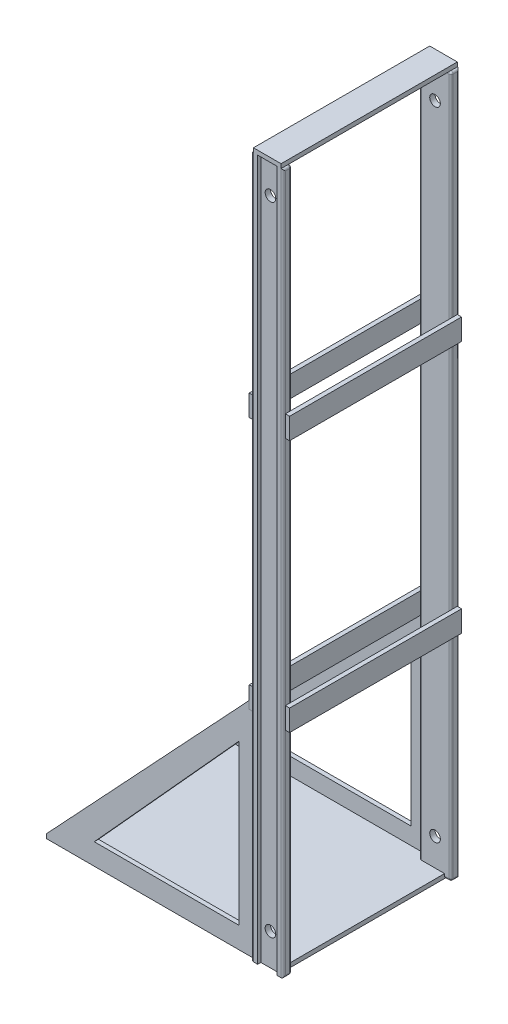
SolidWorks part; units mm, degrees
ref_plane "Front Plane" through (0, 0, 0) normal (0, 0, 1) x (1, 0, 0)
ref_plane "Top Plane" through (0, 0, 0) normal (0, 1, 0) x (1, 0, 0)
ref_plane "Right Plane" through (0, 0, 0) normal (1, 0, 0) x (0, 0, -1)
sketch "Sketch1" plane through (0, 0, 0) normal (0, 0, 1) x (1, 0, 0)
  line L1 (0, 0) -> (15, 0)
  line L2 (0, 0) -> (0, 330)
  line L3 (0, 330) -> (15, 330)
  line L4 (15, 0) -> (15, 330)
  dimension "D1" = 330
  dimension "D2" = 15
extrude "slider_body" add sketch "Sketch1" along normal blind 4 contours L4 L3 L2 L1
sketch "Sketch2" plane through (0, 0, 0) normal (0, 0, -1) x (-1, 0, 0)
  line L0 (0, 330) -> (-15, 330) construction
  line L1 (-12, 330) -> (-3, 330)
  line L2 (-12, 330) -> (-12, 0)
  line L3 (-12, 0) -> (-3, 0)
  line L4 (-3, 330) -> (-3, 0)
  line L5 (0, 0) -> (-15, 0) construction
  line L6 (-15, 0) -> (-15, 330) construction
  line L7 (0, 0) -> (0, 330) construction
  dimension "D1" = 3
  dimension "D2" = 3
extrude "slider_indents" cut sketch "Sketch2" against normal blind 1.5
fillet "Fillet5" radius 1 4 edges at (0, 165, 4) (7.5, 330, 4) (15, 165, 4) (7.5, 0, 4)
fillet "Fillet6" radius 1 5 edges at (0.2929, 329.7071, 3.7071) (0.2929, 0.2929, 3.7071) (0, 165, 0) (0, 330, 1.5) (0, 0, 1.5)
fillet "Fillet7" radius 1 5 edges at (14.7071, 0.2929, 3.7071) (14.7071, 329.7071, 3.7071) (15, 165, 0) (15, 0, 1.5) (15, 330, 1.5)
sketch "Sketch3" plane through (0, 0, 1.5) normal (0, 0, -1) x (-1, 0, 0)
  line L0 (-15, 1) -> (-15, 329) construction
  line L1 (-3, 330) -> (-12, 330) construction
  line L4 (-12, 0) -> (-3, 0) construction
  circle A0 centre (-7.5, 315) radius 2.5
  circle A1 centre (-7.5, 15) radius 2.5
  point P6 (-7.5, 330)
  point P11 (-4.5862, 4.9686)
  dimension "D2" = 5
  dimension "D5" = 5
  dimension "D1" = 7.5
  dimension "D3" = 15
  dimension "D4" = 7.5
  dimension "D6" = 15
extrude "Cut-Extrude2" cut sketch "Sketch3" against normal blind 4
sketch "Sketch5" plane through (0, 330, 0) normal (0, 1, 0) x (1, 0, 0)
  line L1 (1, 0) -> (14, 0)
  line L2 (1, 0) -> (1, -41.5)
  line L3 (1, -41.5) -> (14, -41.5)
  line L4 (14, 0) -> (14, -41.5)
  dimension "D1" = 41.5
extrude "Boss-Extrude2" add sketch "Sketch5" along normal blind 2
sketch "Sketch7" plane through (0, 0, 0) normal (-1, 0, 0) x (0, 0, 1)
  line L0 (1, 329) -> (1, 1) construction
  line L1 (1, 220) -> (41.5, 220)
  line L2 (1, 220) -> (1, 230)
  line L3 (1, 230) -> (41.5, 230)
  line L4 (41.5, 220) -> (41.5, 230)
  line L5 (3, 330) -> (41.5, 330) construction
  line L6 (0, 0) -> (0, 330) construction
  line L7 (1, 1) -> (3, 1) construction
  line L8 (1, 101) -> (42.5, 101)
  line L9 (1, 101) -> (1, 111)
  line L10 (1, 111) -> (42.5, 111)
  line L11 (42.5, 101) -> (42.5, 111)
  dimension "D1" = 110
  dimension "D2" = 10
  dimension "D3" = 41.5
  dimension "D4" = 110
  dimension "D5" = 41.5
  dimension "D6" = 10
extrude "Boss-Extrude3" add sketch "Sketch7" along normal blind 2
sketch "Sketch9" plane through (15, 0, 0) normal (1, 0, 0) x (0, 0, -1)
  line L0 (-1, 1) -> (-1, 329) construction
  line L1 (-1, 230) -> (-41.5, 230)
  line L2 (-1, 230) -> (-1, 220)
  line L3 (-1, 220) -> (-41.5, 220)
  line L4 (-41.5, 230) -> (-41.5, 220)
  line L7 (-3, 1) -> (-1, 1) construction
  line L8 (-1, 101) -> (-42.5, 101)
  line L9 (-1, 101) -> (-1, 111)
  line L10 (-1, 111) -> (-42.5, 111)
  line L11 (-42.5, 101) -> (-42.5, 111)
  dimension "D1" = 10
  dimension "D2" = 110
  dimension "D3" = 10
  dimension "D4" = 41.5
extrude "Boss-Extrude4" add sketch "Sketch9" along normal blind 2
mirror "Mirror4" about plane through (1, 332, 41.5) normal (0, 0, -1) of "slider_body", "slider_indents", "Fillet5", "Fillet6", "Fillet7", "Cut-Extrude2", "Boss-Extrude2", "Boss-Extrude3", "Boss-Extrude4"
sketch "Sketch11" plane through (0, 0, 81.5) normal (0, 0, 1) x (1, 0, 0)
  line L1 (12, 0) -> (-98, 0)
  line L2 (12, 0) -> (12, 2)
  line L3 (12, 2) -> (-98, 2)
  line L4 (-98, 0) -> (-98, 2)
  dimension "D2" = 110
extrude "Boss-Extrude5" add sketch "Sketch11" against normal blind 83
sketch "Sketch13" plane through (0, 0, 81.5) normal (0, 0, 1) x (1, 0, 0)
  line L0 (-98, 2) -> (3, 110)
  line L1 (3, 0) -> (3, 330) construction
  line L2 (3, 110) -> (3, 0)
  line L3 (3, 0) -> (-98, 0)
  line L4 (-98, 0) -> (1, 0) construction
  line L5 (-98, 0) -> (-98, 2)
  dimension "D1" = 110
extrude "Boss-Extrude6" add sketch "Sketch13" against normal blind 2
sketch "Sketch14" plane through (0, 0, -1.5) normal (0, 0, -1) x (-1, 0, 0)
  line L1 (98, 0) -> (98, 2)
  line L2 (98, 2) -> (0, 110)
  line L3 (0, 110) -> (0, 0)
  line L4 (0, 0) -> (98, 0)
  dimension "D1" = 110
extrude "Boss-Extrude7" add sketch "Sketch14" against normal blind 2
sketch "Sketch16" plane through (0, 0, -1.5) normal (0, 0, -1) x (-1, 0, 0)
  line L0 (7.4205, 85) -> (7.4205, 10)
  line L1 (7.4205, 10) -> (75.476, 10)
  line L2 (75.476, 10) -> (7.4205, 85)
  line L3 (98, 0) -> (-12, 0) construction
  line L4 (98, 2) -> (0, 110) construction
  dimension "D1" = 10
  dimension "D2" = 180
  dimension "D3" = 75
  dimension "D4" = 90
extrude "Cut-Extrude3" cut sketch "Sketch16" against normal blind 83
equation "\"arm_h\"=330"
equation "\"D1@Sketch1\"=\"arm_h\""
equation "\"arm_support_w\"=15"
equation "\"D2@Sketch1\"=\"arm_support_w\""
equation "\"slider_thickness\"=4"
equation "\"D1@slider_body\" = \"slider_thickness\""
equation "\"fillet_size\"=1"
equation "\"D1@Fillet5\"=\"fillet_size\""
equation "\"D1@Fillet6\"= \"fillet_size\""
equation "\"D1@Fillet7\"= \"fillet_size\""
equation "\"D1@Sketch3\"= \"arm_support_w\"/2"
equation "\"D3@Sketch3\"=\"arm_support_w\""
equation "\"D4@Sketch3\"= \"arm_support_w\"/2"
equation "\"pin_size_outer\"=5"
equation "\"D5@Sketch3\"=\"pin_size_outer\""
equation "\"D2@Sketch3\"= \"pin_size_outer\""
equation "\"D6@Sketch3\"=\"arm_support_w\""
equation "\"D1@Cut-Extrude2\"= \"slider_thickness\""
equation "\"dist_btw_sliders\"= 75"
equation "\"D1@Sketch5\"= \"slider_thickness\" + \"dist_btw_sliders\"/2"
equation "\"metal_t\"=2"
equation "\"D1@Boss-Extrude2\"=\"metal_t\""
equation "\"D1@Sketch7\"= \"arm_h\"/3"
equation "\"bracket_width\"=10"
equation "\"D2@Sketch7\"=\"bracket_width\""
equation "\"D3@Sketch7\"= \"slider_thickness\" + \"dist_btw_sliders\"/2"
equation "\"D1@Boss-Extrude3\"= \"metal_t\""
equation "\"D1@Sketch9\"= \"bracket_width\""
equation "\"D1@Boss-Extrude4\"= \"metal_t\""
equation "\"D4@Sketch7\"= \"arm_h\"/3"
equation "\"D5@Sketch7\"= \"slider_thickness\" + \"dist_btw_sliders\"/2"
equation "\"D6@Sketch7\"= \"bracket_width\""
equation "\"D2@Sketch9\"= \"arm_h\"/3"
equation "\"D3@Sketch9\"= \"bracket_width\""
equation "\"D4@Sketch9\"= \"slider_thickness\" + \"dist_btw_sliders\"/2"
equation "\"D1@Sketch11\"=\"metal_t\""
equation "\"D2@Sketch11\"= \"arm_h\"/3"
equation "\"D1@Boss-Extrude5\"=\"dist_btw_sliders\" + \"slider_thickness\"*2"
equation "\"D1@Sketch13\"=\"arm_h\"/3"
equation "\"D1@Boss-Extrude6\"=\"metal_t\""
equation "\"D1@Sketch14\"= \"arm_h\"/3"
equation "\"D1@Boss-Extrude7\"= \"metal_t\""
equation "\"D1@Sketch16\"=\"arm_support_w\"*2/3"
equation "\"D1@Cut-Extrude3\"= \"slider_thickness\"*2 + \"dist_btw_sliders\""
